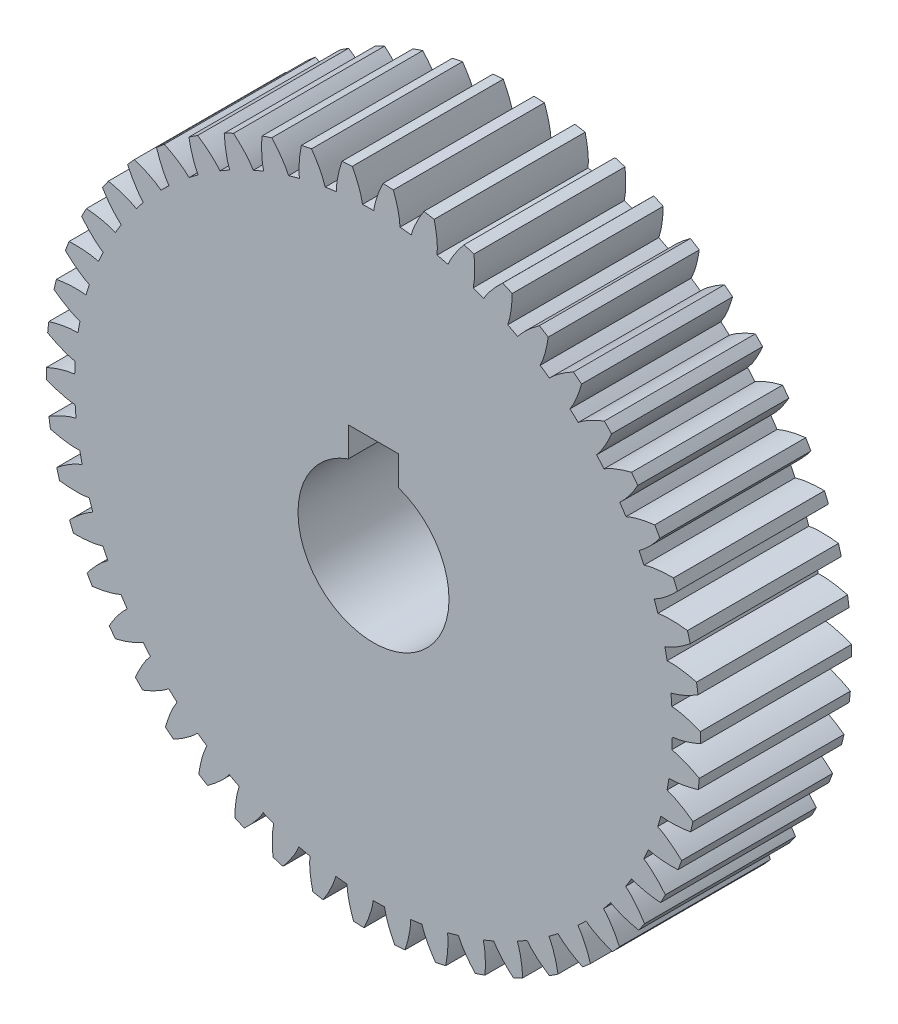
SolidWorks part; units mm, degrees
ref_plane "Front Plane" through (0, 0, 0) normal (0, 0, 1) x (1, 0, 0)
ref_plane "Top Plane" through (0, 0, 0) normal (0, 1, 0) x (1, 0, 0)
ref_plane "Right Plane" through (0, 0, 0) normal (1, 0, 0) x (0, 0, -1)
sketch "Involute Geometry" plane through (0, 0, 0) normal (0, 0, 1) x (1, 0, 0)
  line L0 (0, 23.4923) -> (0, 0) construction
  line L1 (0, 0) -> (1.1665, 25.9738) construction
  line L2 (2.1059, 23.3977) -> (0, 0) construction
  line L3 (0.3366, 24.9977) -> (0, 0) construction
  line L4 (0, 0) -> (1.9056, 24.9273) construction
  circle A1 centre (0, 0) radius 23.4923 construction
  circle A2 centre (0, 0) radius 25 construction
  circle A3 centre (0, 0) radius 26 construction
  circle A4 centre (0, 0) radius 23.75 construction
  arc A5 (0.7536, 25.9891) -> (1.5791, 25.952) centre (0, 0) cw
  arc A6 (0.3366, 24.9977) -> (1.9056, 24.9273) centre (0, 0) cw construction
  spline S0 degree 4 poles (0, 23.4923) (0, 23.5114) (0.0013, 23.5648) (0.0089, 23.6656) (0.0287, 23.8296) (0.081, 24.1325) (0.1926, 24.5862) (0.3554, 25.0766) (0.5626, 25.5852) (0.7677, 26.0245) (0.9438, 26.37) (1.171, 26.7822) (1.4642, 27.2682) (1.8332, 27.8211) (2.2875, 28.4323) (2.7797, 29.0321) (3.2982, 29.6089) (3.8411, 30.1634) (4.4053, 30.6951) (4.9175, 31.1416) (5.3665, 31.5096) (5.7503, 31.8087) (6.0572, 32.04) (6.3766, 32.2711) (6.6846, 32.4876) (7.0225, 32.7147) (7.3185, 32.909) (7.7622, 33.1868) (8.0307, 33.348) (8.4647, 33.6019) (8.6612, 33.7084) (8.8384, 33.8077) (8.891, 33.8352) (8.9294, 33.8561) (8.9501, 33.8675) knots 0 0 0 0 0 0.005377 0.015084 0.028532 0.04661 0.092111 0.146842 0.174209 0.201575 0.228941 0.256307 0.307035 0.361767 0.4165 0.471232 0.525964 0.580697 0.635429 0.690161 0.717528 0.744894 0.77226 0.799626 0.826992 0.854358 0.881725 0.909091 0.954545 0.977273 0.988636 0.994318 1 1 1 1 1 construction
  spline S1 degree 4 poles (0, 23.4923) (0, 23.5114) (0.0013, 23.5648) (0.0089, 23.6656) (0.0287, 23.8296) (0.081, 24.1325) (0.1926, 24.5862) (0.3554, 25.0766) (0.5626, 25.5852) (0.7677, 26.0245) (0.9438, 26.37) (1.171, 26.7822) (1.4642, 27.2682) (1.8332, 27.8211) (2.2875, 28.4323) (2.7797, 29.0321) (3.2982, 29.6089) (3.8411, 30.1634) (4.4053, 30.6951) (4.9175, 31.1416) (5.3665, 31.5096) (5.7503, 31.8087) (6.0572, 32.04) (6.3766, 32.2711) (6.6846, 32.4876) (7.0225, 32.7147) (7.3185, 32.909) (7.6041, 33.0878) (7.7558, 33.1811) (7.8311, 33.2268) knots 0 0 0 0 0 0.005377 0.015084 0.028532 0.04661 0.092111 0.146842 0.174209 0.201575 0.228941 0.256307 0.307035 0.361767 0.4165 0.471232 0.525964 0.580697 0.635429 0.690161 0.717528 0.744894 0.77226 0.799626 0.826992 0.854358 0.881725 0.909091 0.909091 0.909091 0.909091 0.909091
  spline S3 degree 4 poles (2.1059, 23.3977) (2.1076, 23.4167) (2.1111, 23.47) (2.1125, 23.5712) (2.1075, 23.7362) (2.0826, 24.0426) (2.0121, 24.5045) (1.8939, 25.0075) (1.7332, 25.5326) (1.5683, 25.9886) (1.4238, 26.3485) (1.2345, 26.7793) (0.9861, 27.2897) (0.6681, 27.8734) (0.2705, 28.5229) (-0.166, 29.1644) (-0.6307, 29.7854) (-1.1217, 30.3863) (-1.636, 30.9664) (-2.1061, 31.457) (-2.5203, 31.8638) (-2.8757, 32.1961) (-3.1606, 32.454) (-3.4581, 32.7128) (-3.7454, 32.9561) (-4.0616, 33.2125) (-4.339, 33.4325) (-4.756, 33.749) (-5.009, 33.9336) (-5.4185, 34.2255) (-5.6047, 34.3491) (-5.7723, 34.4639) (-5.8222, 34.4959) (-5.8585, 34.5202) (-5.8781, 34.5334) knots 0 0 0 0 0 0.005377 0.015084 0.028532 0.04661 0.092111 0.146842 0.174209 0.201575 0.228941 0.256307 0.307035 0.361767 0.4165 0.471232 0.525964 0.580697 0.635429 0.690161 0.717528 0.744894 0.77226 0.799626 0.826992 0.854358 0.881725 0.909091 0.954545 0.977273 0.988636 0.994318 1 1 1 1 1 construction
  spline S4 degree 4 poles (2.1059, 23.3977) (2.1076, 23.4167) (2.1111, 23.47) (2.1125, 23.5712) (2.1075, 23.7362) (2.0826, 24.0426) (2.0121, 24.5045) (1.8939, 25.0075) (1.7332, 25.5326) (1.5683, 25.9886) (1.4238, 26.3485) (1.2345, 26.7793) (0.9861, 27.2897) (0.6681, 27.8734) (0.2705, 28.5229) (-0.166, 29.1644) (-0.6307, 29.7854) (-1.1217, 30.3863) (-1.636, 30.9664) (-2.1061, 31.457) (-2.5203, 31.8638) (-2.8757, 32.1961) (-3.1606, 32.454) (-3.4581, 32.7128) (-3.7454, 32.9561) (-4.0616, 33.2125) (-4.339, 33.4325) (-4.6074, 33.6362) (-4.7502, 33.7427) (-4.8211, 33.795) knots 0 0 0 0 0 0.005377 0.015084 0.028532 0.04661 0.092111 0.146842 0.174209 0.201575 0.228941 0.256307 0.307035 0.361767 0.4165 0.471232 0.525964 0.580697 0.635429 0.690161 0.717528 0.744894 0.77226 0.799626 0.826992 0.854358 0.881725 0.909091 0.909091 0.909091 0.909091 0.909091
  dimension "D5" = 3.6
sketch "Sketch2" plane through (0, 0, 0) normal (0, 0, 1) x (1, 0, 0)
  circle A0 centre (0, 0) radius 23.75 construction
  circle A1 centre (0, 0) radius 23.75
extrude "Boss-Extrude1" add sketch "Sketch2" along normal mid plane 12
sketch "Sketch3" plane through (0, 0, 0) normal (0, 0, 1) x (1, 0, 0)
  arc A3 (0.0199, 23.75) -> (2.1092, 23.6562) centre (0, 0) cw
  arc A4 (1.5791, 25.952) -> (0.7536, 25.9891) centre (0, 0) ccw construction
  arc A5 (1.5791, 25.952) -> (0.7536, 25.9891) centre (0, 0) ccw
  circle A7 centre (0, 0) radius 23.75 construction
  spline S0 degree 4 poles (999.8204, 40.2462) (20.7121, 20.125) (0.4503, 21.1025) (-0.1347, 22.474) (0.0287, 23.8296) (0.081, 24.1325) (0.1926, 24.5862) (0.3554, 25.0766) (0.5626, 25.5852) (0.7677, 26.0245) (0.9438, 26.37) (1.171, 26.7822) (1.4642, 27.2682) (1.8332, 27.8211) (2.2875, 28.4323) (2.7797, 29.0321) (3.2982, 29.6089) (3.8411, 30.1634) (4.4053, 30.6951) (4.9175, 31.1416) (5.3665, 31.5096) (5.7503, 31.8087) (6.0572, 32.04) (6.3766, 32.2711) (6.6846, 32.4876) (7.0225, 32.7147) (8.3806, 33.6059) (11.7895, 35.5553) (-19.6779, 16.1915) (862.8738, 551.731) knots -0.338747 -0.338747 -0.338747 -0.338747 -0.338747 0.005377 0.015084 0.028532 0.04661 0.092111 0.146842 0.174209 0.201575 0.228941 0.256307 0.307035 0.361767 0.4165 0.471232 0.525964 0.580697 0.635429 0.690161 0.717528 0.744894 0.77226 0.799626 0.826992 0.854358 0.881725 1.301773 1.301773 1.301773 1.301773 1.301773 only from (0, 23.4923) to (7.5082, 22.3415) construction
  spline S1 degree 4 poles (0.0199, 23.75) (0.0244, 23.7861) (0.0384, 23.8856) (0.0837, 24.1434) (0.1926, 24.5862) (0.3677, 25.1136) (0.5556, 25.5675) (0.6944, 25.8667) (0.7536, 25.9891) knots 0.018251 0.018251 0.018251 0.018251 0.018251 0.028532 0.04661 0.092111 0.146842 0.185208 0.185208 0.185208 0.185208 0.185208
  spline S3 degree 4 poles (-992.1874, 129.7099) (-18.8247, 21.9006) (1.4432, 21.0579) (2.1488, 22.3715) (2.1075, 23.7362) (2.0826, 24.0426) (2.0121, 24.5045) (1.8939, 25.0075) (1.7332, 25.5326) (1.5683, 25.9886) (1.4238, 26.3485) (1.2345, 26.7793) (0.9861, 27.2897) (0.6681, 27.8734) (0.2705, 28.5229) (-0.166, 29.1644) (-0.6307, 29.7854) (-1.1217, 30.3863) (-1.636, 30.9664) (-2.1061, 31.457) (-2.5203, 31.8638) (-2.8757, 32.1961) (-3.1606, 32.454) (-3.4581, 32.7128) (-3.7454, 32.9561) (-4.0616, 33.2125) (-5.3344, 34.2219) (-8.5548, 36.469) (21.0501, 14.3623) (-809.9417, 626.8594) knots -0.338747 -0.338747 -0.338747 -0.338747 -0.338747 0.005377 0.015084 0.028532 0.04661 0.092111 0.146842 0.174209 0.201575 0.228941 0.256307 0.307035 0.361767 0.4165 0.471232 0.525964 0.580697 0.635429 0.690161 0.717528 0.744894 0.77226 0.799626 0.826992 0.854358 0.881725 1.301773 1.301773 1.301773 1.301773 1.301773 only from (2.1059, 23.3977) to (-4.8211, 33.795) construction
  spline S4 degree 4 poles (2.1092, 23.6562) (2.1079, 23.6925) (2.1029, 23.7929) (2.0809, 24.0537) (2.0121, 24.5045) (1.885, 25.0455) (1.7385, 25.5144) (1.6271, 25.8248) (1.5791, 25.952) knots 0.018251 0.018251 0.018251 0.018251 0.018251 0.028532 0.04661 0.092111 0.146842 0.185208 0.185208 0.185208 0.185208 0.185208
extrude "Boss-Extrude2" add sketch "Sketch3" along normal through all and the other way through all
fillet "Fillet2" [suppressed] radius 0.381
pattern_circular "CirPattern1" count 50 over 360 about axis through (0, 0, 6) along (0, 0, -1) of "Boss-Extrude2", "Fillet2"
ref_axis "Axis1" through (0, 0, 6) along (0, 0, -1)
sketch "Sketch4" plane through (0, 0, -6) normal (0, 0, -1) x (-1, 0, 0)
  circle A1 centre (0, 0) radius 6
  dimension "D1" = 12
extrude "Cut-Extrude1" cut sketch "Sketch4" against normal through all
sketch "Sketch5" plane through (0, 0, -6) normal (0, 0, -1) x (-1, 0, 0)
  line L1 (-2, 8) -> (2, 8)
  line L2 (-2, 8) -> (-2, 5.6569)
  line L3 (-2, 5.6569) -> (2, 5.6569)
  line L4 (2, 8) -> (2, 5.6569)
  line L5 (-2, 8) -> (2, 5.6569) construction
  line L6 (-2, 5.6569) -> (2, 8) construction
  circle A0 centre (0, 0) radius 6 construction
  point P0 (0, 6.8284)
  point P7 (0, 0)
  dimension "D1" = 4
  dimension "D2" = 2
extrude "Cut-Extrude2" cut sketch "Sketch5" against normal through all
equation "\"N\" = 50'Number of Teeth"
equation "\"m\"= 1mm'Diametral Pitch"
equation "\"phi\"= 20deg'Pressure Angle"
equation "\"a\"= \"m\"'Addendum"
equation "\"b\"= 1.25 * \"m\"'Dedendum"
equation "\"Dp\"= \"N\" * \"m\"'Pitch diameter"
equation "\"Db\"= \"Dp\" * cos ( \"phi\" )'Base diameter"
equation "\"D1@Involute Geometry\" = \"Db\""
equation "\"D2@Involute Geometry\" = \"Dp\""
equation "\"D3@Involute Geometry\" = \"Dp\" + 2 * \"a\""
equation "\"D4@Involute Geometry\" = \"Dp\" - 2 * \"b\""
equation "\"D1@CirPattern1\"=\"N\""
equation "\"D5@Involute Geometry\"=180/\"N\""
equation "\"D1@Boss-Extrude1\"=12*\"m\""
equation "\"alpha\"= sqr ( \"Dp\" ^ 2 - \"Db\" ^ 2 ) / \"Db\" * 180 / pi - \"phi\""
equation "\"beta\"= ( ( 360deg / \"N\" ) / 4 - \"alpha\" )"
